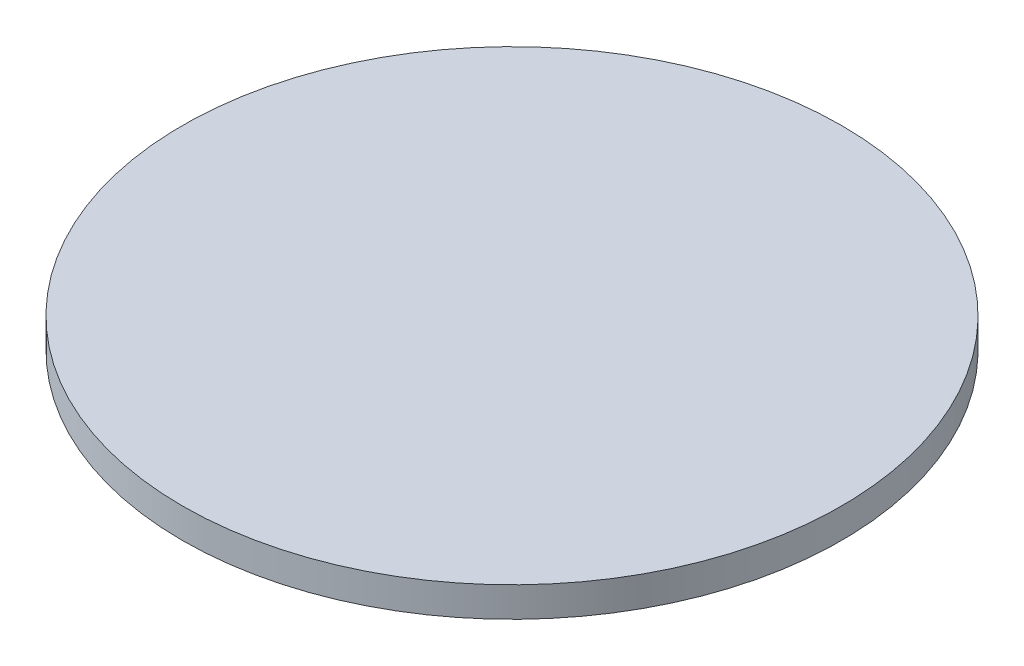
SolidWorks part; units mm, degrees
ref_plane "Front Plane" through (0, 0, 0) normal (0, 0, 1) x (1, 0, 0)
ref_plane "Top Plane" through (0, 0, 0) normal (0, 1, 0) x (1, 0, 0)
ref_plane "Right Plane" through (0, 0, 0) normal (1, 0, 0) x (0, 0, -1)
sketch "Sketch1" plane through (0, 0, 0) normal (0, 1, 0) x (1, 0, 0)
  circle A0 centre (0, 0) radius 2.9369
  dimension "D1" = 5.8738
extrude "cap" add sketch "Sketch1" along normal blind 0.2666
equation "\"magnet_inset\"= 0.0625in"
equation "\"magnet_diameter\" = 0.2in"
equation "\"steel_inset_distance\" = 1in / 32"
equation "\"kapton_thickness\"= 0.005in"
equation "\"pcb_thickness\"= 0.6mm"
equation "\"magnet_thickness\" = 0.03125in"
equation "\"D1@Sketch1\"=(\"magnet_diameter\") + (\"steel_inset_distance\")"
equation "\"D1@cap\"=( \"pcb_thickness\"+\"kapton_thickness\"/2)-(\"magnet_thickness\"/2)"
equation "\"edge_radius\" = 1in / 10"
equation "\"card_width\" = 78mm"
equation "\"card_height\" = 50mm"
equation "\"battery_diameter\" = 20mm"
equation "\"battery_oversize\" = 0.1mm"
equation "\"battery_vertical_inset\" = 1in / 16"
equation "\"battery_horizontal_inset\" = 1in / 4"
equation "\"battery_spacing\" = 1in / 16"
equation "\"battery_thickness\" = 1.6mm"
